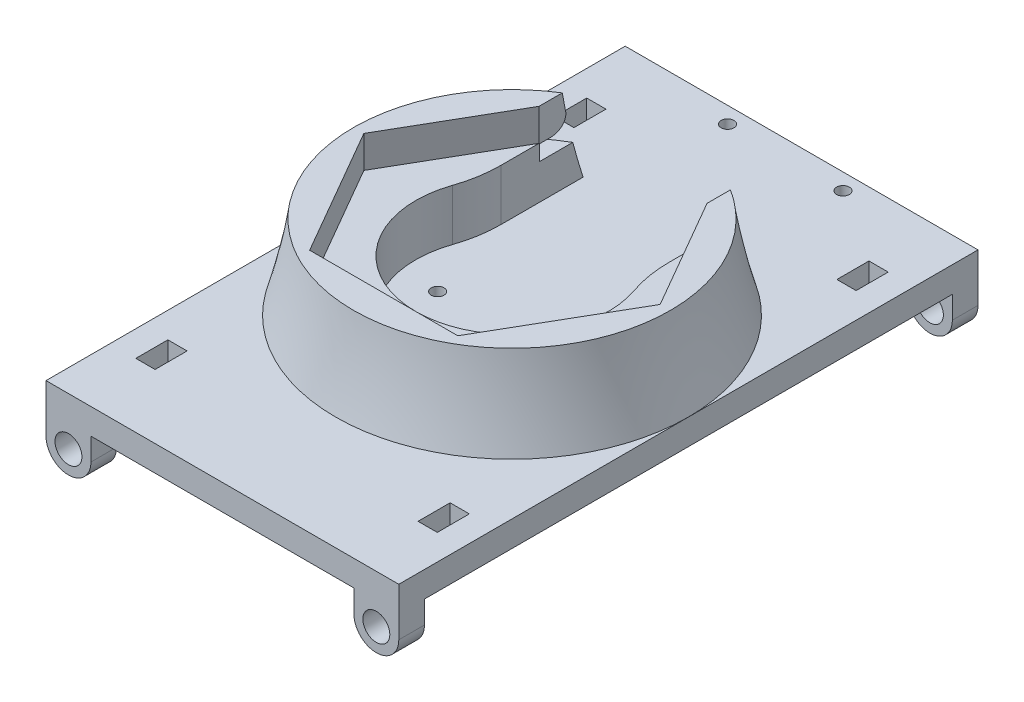
SolidWorks part; units mm, degrees
material "ABS"
ref_plane "前视基准面" through (0, 0, 0) normal (0, 0, 1) x (1, 0, 0)
ref_plane "上视基准面" through (0, 0, 0) normal (0, 1, 0) x (1, 0, 0)
ref_plane "右视基准面" through (0, 0, 0) normal (1, 0, 0) x (0, 0, -1)
sketch "草图1" plane through (0, 0, 0) normal (0, 1, 0) x (1, 0, 0)
  line L1 (-27.5, -41.15) -> (27.5, -41.15)
  line L2 (-27.5, -41.15) -> (-27.5, 41.15)
  line L3 (-27.5, 41.15) -> (27.5, 41.15)
  line L4 (27.5, -41.15) -> (27.5, 41.15)
  line L5 (-27.5, -41.15) -> (27.5, 41.15) construction
  line L6 (-27.5, 41.15) -> (27.5, -41.15) construction
  point P0 (0, 0)
  dimension "D1" = 82.3
  dimension "D2" = 55
extrude "凸台-拉伸1" add sketch "草图1" along normal blind 4
sketch "草图2" plane through (0, 0, 41.15) normal (0, 0, 1) x (1, 0, 0)
  line L0 (0, 0) -> (0, -3.5)
  line L1 (-27.5, 4) -> (27.5, 4)
  line L2 (-27.5, 4) -> (-27.5, 0)
  line L3 (-27.5, 0) -> (27.5, 0)
  line L4 (27.5, 4) -> (27.5, 0)
  line L5 (-24, -3.5) -> (24, -3.5)
  line L6 (27.5, 0) -> (27.5, -3.5)
  line L7 (20.5, -3.5) -> (20.5, 0)
  line L8 (0, 0) -> (0, 4)
  circle A2 centre (24, -3.5) radius 2.1
  circle A3 centre (24, -3.5) radius 3.5
  point P10 (0, -3.5)
  line M10 (-27.5, 0) -> (27.5, 0)
  line M11 (27.5, 0) -> (27.5, 4)
  line M12 (27.5, 4) -> (-27.5, 4)
  dimension "D1" = 48
  dimension "D2" = 4.2
  dimension "D3" = 3.5
extrude "凸台-拉伸2" add sketch "草图2" along normal blind 4 contours L8 L3 M10 M11 M12 | A3 L3 L7 | A3 L6 M10 | A3 A2 region at (13.75, 2, 41.15) region at (21.2818, -0.7818, 41.15) region at (21.5951, -1.0951, 41.15) region at (26.7182, -0.7818, 41.15)
mirror "镜向1" about plane through (0, 0, 45.15) normal (-1, 0, 0) of "凸台-拉伸2"
sketch "草图3" plane through (0, 4, 0) normal (0, 1, 0) x (1, 0, 0)
  line L0 (0, 0) -> (18.6883, 0)
ref_plane "基准面2" through (0, 0, 0) normal (0, 0, 1) x (1, 0, 0)
mirror "镜向4" about plane through (0, 0, 0) normal (0, 0, 1) of bodies 108
sketch "草图4" plane through (0, 4, 0) normal (0, 1, 0) x (1, 0, 0)
  line L0 (27.5, 45.15) -> (-27.5, 45.15) construction
  line L1 (-22.5, -3.15) -> (22.5, -3.15)
  line L2 (-22.5, -3.15) -> (-22.5, -13.15)
  line L3 (-22.5, -13.15) -> (22.5, -13.15)
  line L4 (22.5, -3.15) -> (22.5, -13.15)
  line L5 (-27.5, 45.15) -> (-27.5, -45.15) construction
  line L6 (27.5, -45.15) -> (27.5, 45.15) construction
  dimension "D1" = 58.3
  dimension "D2" = 5
  dimension "D3" = 5
  dimension "D4" = 10
sketch "草图5" plane through (0, 4, 0) normal (0, 1, 0) x (1, 0, 0)
  line L5 (-9, 42.6) -> (-9, -2.6)
  line L6 (-9, 42.6) -> (9, 42.6)
  line L7 (-9, -2.6) -> (9, -2.6)
  line L8 (9, 42.6) -> (9, -2.6)
  line L9 (-9, 42.6) -> (9, -2.6) construction
  line L10 (-9, -2.6) -> (9, 42.6) construction
  line L11 (0, 0) -> (0, 20)
  line L12 (-24.8329, 0) -> (24.8329, 0) construction
  line L13 (27.5, 45.15) -> (-27.5, 45.15) construction
  circle A0 centre (-9, 42.6) radius 1
  circle A1 centre (9, 42.6) radius 1
  circle A2 centre (9, -2.6) radius 1
  circle A3 centre (-9, -2.6) radius 1
  point P1 (0, 20)
  dimension "D5" = 2
  dimension "D6" = 2
  dimension "D7" = 2
  dimension "D8" = 2
  dimension "D1" = 45.2
  dimension "D2" = 18
  dimension "D3" = 90
  dimension "D4" = 90
  dimension "D9" = 20
extrude "切除-拉伸2" cut sketch "草图5" against normal blind 10 contours L6 A1 L8 | L8 A1 L6 | L5 A3 L7 | L7 A3 L5 | L7 A2 L8 | L8 A2 L7 | A0 region at (-8.5756, 4, 2.1756) region at (-9.1415, 4, 2.7415) region at (9.1415, 4, -42.7415) region at (8.5756, 4, -42.1756) region at (8.5756, 4, 2.1756) region at (9.1415, 4, 2.7415)
ref_plane "基准面3" through (0, 17, 0) normal (0, 1, 0) x (1, 0, 0)
sketch "草图7" plane through (0, 17, 0) normal (0, 1, 0) x (1, 0, 0)
  arc A45 (14.1766, -20.2266) -> (15.5749, -19.1706) centre (0, 0) ccw
  arc A46 (20.5259, -13.7396) -> (21.4484, -12.2498) centre (0, 0) ccw
  arc A47 (24.1032, -5.397) -> (24.4251, -3.6746) centre (0, 0) ccw
  arc A48 (24.4251, 3.6746) -> (24.1032, 5.397) centre (0, 0) ccw
  arc A49 (21.4484, 12.2498) -> (20.5259, 13.7396) centre (0, 0) ccw
  arc A50 (15.5749, 19.1706) -> (14.1766, 20.2266) centre (0, 0) ccw
  arc A51 (7.5979, 23.5024) -> (5.9126, 23.9819) centre (0, 0) ccw
  arc A52 (-1.4052, 24.66) -> (-3.15, 24.4983) centre (0, 0) ccw
  arc A53 (-10.2185, 22.4871) -> (-11.7871, 21.7061) centre (0, 0) ccw
  arc A54 (-17.6518, 17.2773) -> (-18.8323, 15.9824) centre (0, 0) ccw
  arc A55 (-22.7011, 9.734) -> (-23.3341, 8.1001) centre (0, 0) ccw
  arc A56 (-24.6845, 0.8761) -> (-24.6845, -0.8761) centre (0, 0) ccw
  arc A57 (-23.3341, -8.1001) -> (-22.7011, -9.734) centre (0, 0) ccw
  arc A58 (-18.8323, -15.9824) -> (-17.6518, -17.2773) centre (0, 0) ccw
  arc A59 (-11.7871, -21.7061) -> (-10.2185, -22.4871) centre (0, 0) ccw
  arc A60 (-3.15, -24.4983) -> (-1.4052, -24.66) centre (0, 0) ccw
  arc A61 (5.9126, -23.9819) -> (7.5979, -23.5024) centre (0, 0) ccw
  spline S0 degree 3 number of poles 73 (7.5979, -23.5024) -> (14.1766, -20.2266)
  spline S1 degree 3 number of poles 73 (15.5749, -19.1706) -> (20.5259, -13.7396)
  spline S2 degree 3 number of poles 73 (21.4484, -12.2498) -> (24.1032, -5.397)
  spline S3 degree 3 number of poles 73 (24.4251, -3.6746) -> (24.4251, 3.6746)
  spline S4 degree 3 number of poles 73 (24.1032, 5.397) -> (21.4484, 12.2498)
  spline S5 degree 3 number of poles 73 (20.5259, 13.7396) -> (15.5749, 19.1706)
  spline S6 degree 3 number of poles 73 (14.1766, 20.2266) -> (7.5979, 23.5024)
  spline S7 degree 3 number of poles 73 (5.9126, 23.9819) -> (-1.4052, 24.66)
  spline S8 degree 3 number of poles 73 (-3.15, 24.4983) -> (-10.2185, 22.4871)
  spline S9 degree 3 number of poles 73 (-11.7871, 21.7061) -> (-17.6518, 17.2773)
  spline S10 degree 3 number of poles 73 (-18.8323, 15.9824) -> (-22.7011, 9.734)
  spline S11 degree 3 number of poles 73 (-23.3341, 8.1001) -> (-24.6845, 0.8761)
  spline S12 degree 3 number of poles 73 (-24.6845, -0.8761) -> (-23.3341, -8.1001)
  spline S13 degree 3 number of poles 73 (-22.7011, -9.734) -> (-18.8323, -15.9824)
  spline S14 degree 3 number of poles 73 (-17.6518, -17.2773) -> (-11.7871, -21.7061)
  spline S15 degree 3 number of poles 73 (-10.2185, -22.4871) -> (-3.15, -24.4983)
  spline S16 degree 3 number of poles 73 (-1.4052, -24.66) -> (5.9126, -23.9819)
  dimension "D1" = 0
extrude "凸台-拉伸4" add sketch "草图7" along normal blind 5 separate body contours S8 A53 S9 A54 S10 A55 S11 A56 S12 A57 S13 A58 S14 A59 S15 A60 S16 A61 S0 A45 S1 A46 S2 A47 S3 A48 S4 A49 S5 A50 S6 A51 S7 A52
sketch "草图9" plane through (0, 22, 0) normal (0, 1, 0) x (1, 0, 0)
  circle A0 centre (0, 0) radius 15
  dimension "D1" = 30
extrude "切除-拉伸4" cut sketch "草图9" against normal blind 10
sketch "草图11" plane through (0, 4, 0) normal (0, 1, 0) x (1, 0, 0)
  circle A0 centre (0, 0) radius 27.5
sketch "草图12" plane through (0, 17, 0) normal (0, -1, 0) x (1, 0, 0)
  circle A1 centre (0, 0) radius 24.7
  dimension "D1" = 49.4
loft "放样2" add profiles "草图11", "草图12" connector at (-10.3319, 4, 25.4853) connector at (-14.8676, 17, 19.7242)
sketch "草图14" plane through (0, 17, 0) normal (0, 1, 0) x (1, 0, 0)
  circle A0 centre (0, 0) radius 15
extrude "切除-拉伸5" cut sketch "草图14" against normal up to surface (13 mm away) up to face at (9, 4, -41.6)
sketch "草图15" plane through (0, 17, 0) normal (0, 1, 0) x (1, 0, 0)
  line L0 (27.5, -0.0005) -> (27.5, 45.15) construction
  line L1 (-13.1, 4.2757) -> (13.1, 4.2757)
  line L2 (-13.1, 4.2757) -> (-13.1, 49.1916)
  line L3 (-13.1, 49.1916) -> (13.1, 49.1916)
  line L4 (13.1, 4.2757) -> (13.1, 49.1916)
  line L5 (-27.5, 45.15) -> (-27.5, 0.0005) construction
  dimension "D1" = 14.4
  dimension "D2" = 44.916
  dimension "D3" = 14.4
extrude "切除-拉伸6" cut sketch "草图15" against normal up to surface (13 mm away) up to face at (9, 4, -41.6)
sketch "草图16" plane through (-13.1, 0, 0) normal (1, 0, 0) x (0, 0, -1)
  line L0 (24.1793, 4) -> (-0.0005, 4) construction
  line L1 (17.35, 9.5) -> (26.3941, 9.5)
  line L2 (17.35, 9.5) -> (17.35, 11.9)
  line L3 (17.35, 11.9) -> (26.3941, 11.9)
  line L4 (26.3941, 9.5) -> (26.3941, 11.9)
  line L5 (-0.0005, 4) -> (45.15, 4) construction
  line L6 (45.15, -3.5) -> (45.15, 4) construction
  dimension "D1" = 7.9
  dimension "D2" = 5.5
  dimension "D3" = 27.8
extrude "切除-拉伸7" cut sketch "草图16" against normal blind 5
fillet "圆角1" radius 2 1 edges at (-15.721, 11.9, -20.1857)
fillet "圆角2" radius 20 2 edges at (-13.1, 10.5, -7.3068) (13.1, 10.5, -7.3068)
sketch "草图17" plane through (0, 22, 0) normal (0, 1, 0) x (1, 0, 0)
  arc A17 (-17.6518, 17.2773) -> (-18.8323, 15.9824) centre (0, 0) ccw
  arc A18 (-17.6518, 17.2773) -> (-18.8323, 15.9824) centre (0, 0) ccw
  arc A19 (-22.7011, 9.734) -> (-23.3341, 8.1001) centre (0, 0) ccw
  arc A20 (-22.7011, 9.734) -> (-23.3341, 8.1001) centre (0, 0) ccw
  arc A21 (-24.6845, 0.8761) -> (-24.6845, -0.8761) centre (0, 0) ccw
  arc A22 (-24.6845, 0.8761) -> (-24.6845, -0.8761) centre (0, 0) ccw
  arc A23 (-23.3341, -8.1001) -> (-22.7011, -9.734) centre (0, 0) ccw
  arc A24 (-23.3341, -8.1001) -> (-22.7011, -9.734) centre (0, 0) ccw
  arc A25 (-18.8323, -15.9824) -> (-17.6518, -17.2773) centre (0, 0) ccw
  arc A26 (-18.8323, -15.9824) -> (-17.6518, -17.2773) centre (0, 0) ccw
  arc A27 (-11.7871, -21.7061) -> (-10.2185, -22.4871) centre (0, 0) ccw
  arc A28 (-11.7871, -21.7061) -> (-10.2185, -22.4871) centre (0, 0) ccw
  arc A29 (-3.15, -24.4983) -> (-1.4052, -24.66) centre (0, 0) ccw
  arc A30 (-3.15, -24.4983) -> (-1.4052, -24.66) centre (0, 0) ccw
  arc A31 (5.9126, -23.9819) -> (7.5979, -23.5024) centre (0, 0) ccw
  arc A32 (5.9126, -23.9819) -> (7.5979, -23.5024) centre (0, 0) ccw
  arc A45 (-1.4052, 24.66) -> (-3.15, 24.4983) centre (0, 0) ccw
  arc A46 (-10.2185, 22.4871) -> (-11.7871, 21.7061) centre (0, 0) ccw
  arc A83 (14.1766, -20.2266) -> (15.5749, -19.1706) centre (0, 0) ccw
  arc A84 (20.5259, -13.7396) -> (21.4484, -12.2498) centre (0, 0) ccw
  arc A85 (24.1032, -5.397) -> (24.4251, -3.6746) centre (0, 0) ccw
  arc A86 (24.4251, 3.6746) -> (24.1032, 5.397) centre (0, 0) ccw
  arc A87 (21.4484, 12.2498) -> (20.5259, 13.7396) centre (0, 0) ccw
  arc A88 (15.5749, 19.1706) -> (14.1766, 20.2266) centre (0, 0) ccw
  arc A89 (7.5979, 23.5024) -> (5.9126, 23.9819) centre (0, 0) ccw
  arc A90 (-1.4052, 24.66) -> (-3.15, 24.4983) centre (0, 0) ccw
  arc A91 (-10.2185, 22.4871) -> (-11.7871, 21.7061) centre (0, 0) ccw
  arc A128 (14.1766, -20.2266) -> (15.5749, -19.1706) centre (0, 0) ccw
  arc A129 (20.5259, -13.7396) -> (21.4484, -12.2498) centre (0, 0) ccw
  arc A130 (24.1032, -5.397) -> (24.4251, -3.6746) centre (0, 0) ccw
  arc A131 (24.4251, 3.6746) -> (24.1032, 5.397) centre (0, 0) ccw
  arc A132 (21.4484, 12.2498) -> (20.5259, 13.7396) centre (0, 0) ccw
  arc A133 (15.5749, 19.1706) -> (14.1766, 20.2266) centre (0, 0) ccw
  arc A134 (7.5979, 23.5024) -> (5.9126, 23.9819) centre (0, 0) ccw
  spline S17 degree 3 number of poles 73 (-11.7871, 21.7061) -> (-17.6518, 17.2773)
  spline S18 degree 3 number of poles 73 (-11.7871, 21.7061) -> (-17.6518, 17.2773)
  spline S19 degree 3 number of poles 73 (-18.8323, 15.9824) -> (-22.7011, 9.734)
  spline S20 degree 3 number of poles 73 (-18.8323, 15.9824) -> (-22.7011, 9.734)
  spline S21 degree 3 number of poles 73 (-23.3341, 8.1001) -> (-24.6845, 0.8761)
  spline S22 degree 3 number of poles 73 (-23.3341, 8.1001) -> (-24.6845, 0.8761)
  spline S23 degree 3 number of poles 73 (-24.6845, -0.8761) -> (-23.3341, -8.1001)
  spline S24 degree 3 number of poles 73 (-24.6845, -0.8761) -> (-23.3341, -8.1001)
  spline S25 degree 3 number of poles 73 (-22.7011, -9.734) -> (-18.8323, -15.9824)
  spline S26 degree 3 number of poles 73 (-22.7011, -9.734) -> (-18.8323, -15.9824)
  spline S27 degree 3 number of poles 73 (-17.6518, -17.2773) -> (-11.7871, -21.7061)
  spline S28 degree 3 number of poles 73 (-17.6518, -17.2773) -> (-11.7871, -21.7061)
  spline S29 degree 3 number of poles 73 (-10.2185, -22.4871) -> (-3.15, -24.4983)
  spline S30 degree 3 number of poles 73 (-10.2185, -22.4871) -> (-3.15, -24.4983)
  spline S31 degree 3 number of poles 73 (-1.4052, -24.66) -> (5.9126, -23.9819)
  spline S32 degree 3 number of poles 73 (-1.4052, -24.66) -> (5.9126, -23.9819)
  spline S45 degree 3 number of poles 73 (-3.15, 24.4983) -> (-10.2185, 22.4871)
  spline S82 degree 3 number of poles 73 (7.5979, -23.5024) -> (14.1766, -20.2266)
  spline S83 degree 3 number of poles 73 (15.5749, -19.1706) -> (20.5259, -13.7396)
  spline S84 degree 3 number of poles 73 (21.4484, -12.2498) -> (24.1032, -5.397)
  spline S85 degree 3 number of poles 73 (24.4251, -3.6746) -> (24.4251, 3.6746)
  spline S86 degree 3 number of poles 73 (24.1032, 5.397) -> (21.4484, 12.2498)
  spline S87 degree 3 number of poles 73 (20.5259, 13.7396) -> (15.5749, 19.1706)
  spline S88 degree 3 number of poles 73 (14.1766, 20.2266) -> (7.5979, 23.5024)
  spline S89 degree 3 number of poles 73 (5.9126, 23.9819) -> (-1.4052, 24.66)
  spline S90 degree 3 number of poles 73 (-3.15, 24.4983) -> (-10.2185, 22.4871)
  spline S127 degree 3 number of poles 73 (7.5979, -23.5024) -> (14.1766, -20.2266)
  spline S128 degree 3 number of poles 73 (15.5749, -19.1706) -> (20.5259, -13.7396)
  spline S129 degree 3 number of poles 73 (21.4484, -12.2498) -> (24.1032, -5.397)
  spline S130 degree 3 number of poles 73 (24.4251, -3.6746) -> (24.4251, 3.6746)
  spline S131 degree 3 number of poles 73 (24.1032, 5.397) -> (21.4484, 12.2498)
  spline S132 degree 3 number of poles 73 (20.5259, 13.7396) -> (15.5749, 19.1706)
  spline S133 degree 3 number of poles 73 (14.1766, 20.2266) -> (7.5979, 23.5024)
  spline S134 degree 3 number of poles 73 (5.9126, 23.9819) -> (-1.4052, 24.66)
  dimension "D1" = 0
sketch "草图19" plane through (0, 17, 0) normal (0, 1, 0) x (1, 0, 0)
  circle A0 centre (0, 0) radius 31.1484
extrude "切除-拉伸8" cut sketch "草图19" along normal blind 10
sketch "草图20" plane through (0, 17, 0) normal (0, 1, 0) x (1, 0, 0)
  line L1 (23.094, 0) -> (11.547, 20)
  line L2 (11.547, 20) -> (-11.547, 20)
  line L3 (-11.547, 20) -> (-23.094, 0)
  line L4 (-23.094, 0) -> (-11.547, -20)
  line L5 (-11.547, -20) -> (11.547, -20)
  line L6 (11.547, -20) -> (23.094, 0)
  circle A0 centre (0, 0) radius 20 construction
  dimension "D1" = 40
extrude "切除-拉伸9" cut sketch "草图20" against normal blind 5
sketch "草图21" plane through (0, 12, 0) normal (0, 1, 0) x (1, 0, 0)
  line L7 (-13.1, 11.375) -> (-13.1, 17.3101)
  line L8 (-13.1, 17.3101) -> (-23.094, 0)
  line L9 (-23.094, 0) -> (-11.547, -20)
  line L10 (-11.547, -20) -> (11.547, -20)
  line L11 (11.547, -20) -> (23.094, 0)
  line L12 (23.094, 0) -> (13.1, 17.3101)
  line L13 (13.1, 17.3101) -> (13.1, 11.375)
  line L14 (-13.1, 11.375) -> (-13.1, 17.3101)
  line L15 (-13.1, 17.3101) -> (-23.094, 0)
  line L16 (-23.094, 0) -> (-11.547, -20)
  line L17 (-11.547, -20) -> (11.547, -20)
  line L18 (11.547, -20) -> (23.094, 0)
  line L19 (23.094, 0) -> (13.1, 17.3101)
  line L20 (13.1, 17.3101) -> (13.1, 11.375)
  arc A3 (13.1, 11.375) -> (14.1857, 4.875) centre (33.1, 11.375) ccw
  arc A4 (-14.1857, 4.875) -> (14.1857, 4.875) centre (0, 0) ccw
  arc A5 (-14.1857, 4.875) -> (-13.1, 11.375) centre (-33.1, 11.375) ccw
  arc A6 (13.1, 11.375) -> (14.1857, 4.875) centre (33.1, 11.375) ccw
  arc A7 (-14.1857, 4.875) -> (14.1857, 4.875) centre (0, 0) ccw
  arc A8 (-14.1857, 4.875) -> (-13.1, 11.375) centre (-33.1, 11.375) ccw
  dimension "D1" = 0
sketch "草图22" plane through (0, 4, 0) normal (0, 1, 0) x (1, 0, 0)
  line L0 (27.5, -0.0005) -> (27.5, 45.15) construction
  line L1 (-23.5, 35.15) -> (-20.5, 35.15)
  line L2 (-23.5, 35.15) -> (-23.5, 30.15)
  line L3 (-23.5, 30.15) -> (-20.5, 30.15)
  line L4 (-20.5, 35.15) -> (-20.5, 30.15)
  line L5 (23.5, 35.15) -> (20.5, 35.15)
  line L6 (23.5, 35.15) -> (23.5, 30.15)
  line L7 (23.5, 30.15) -> (20.5, 30.15)
  line L8 (20.5, 35.15) -> (20.5, 30.15)
  line L9 (-27.5, 45.15) -> (-27.5, 0.0005) construction
  line L10 (27.5, 45.15) -> (-27.5, 45.15) construction
  dimension "D1" = 7
  dimension "D2" = 7
  dimension "D3" = 3
  dimension "D4" = 5
  dimension "D5" = 3
  dimension "D6" = 5
  dimension "D7" = 10
  dimension "D8" = 10
extrude "切除-拉伸10" cut sketch "草图22" against normal blind 5
mirror "镜向5" about plane through (0, 0, 0) normal (0, 0, 1) of "切除-拉伸10"
